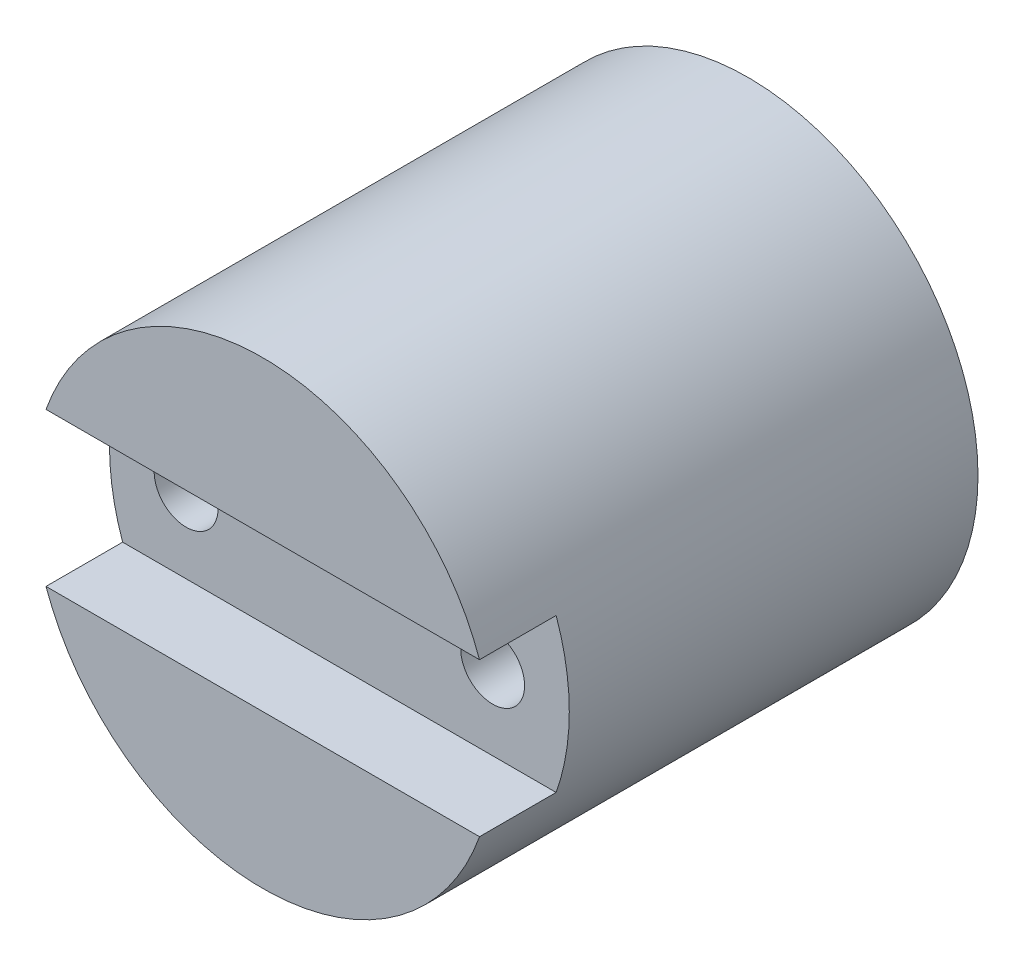
SolidWorks part; units mm, degrees
ref_plane "Front Plane" through (0, 0, 0) normal (0, 0, 1) x (1, 0, 0)
ref_plane "Top Plane" through (0, 0, 0) normal (0, 1, 0) x (1, 0, 0)
ref_plane "Right Plane" through (0, 0, 0) normal (1, 0, 0) x (0, 0, -1)
sketch "Sketch1" plane through (0, 0, 0) normal (0, 0, 1) x (1, 0, 0)
  circle A0 centre (0, 0) radius 9
extrude "Body" add sketch "Sketch1" along normal blind 19
sketch "Sketch2" plane through (0, 0, 0) normal (0, 0, 1) x (1, 0, 0)
  circle A0 centre (0, 0) radius 4
extrude "Bore" cut sketch "Sketch2" along normal blind 12
sketch "Sketch3" plane through (0, 0, 0) normal (0, 0, 1) x (1, 0, 0)
  line L1 (3.2, -4.5) -> (4.7, -4.5)
  line L2 (3.2, -4.5) -> (3.2, 4.5)
  line L3 (3.2, 4.5) -> (4.7, 4.5)
  line L4 (4.7, -4.5) -> (4.7, 4.5)
extrude "Bore_flat" add sketch "Sketch3" along normal blind 12
ref_plane "Plane_z12" through (0, 0, 12) normal (0, 0, 1) x (1, 0, 0)
sketch "Sketch4" plane through (0, 0, 12) normal (0, 0, 1) x (1, 0, 0)
  circle A0 centre (0, 0) radius 3
extrude "Magnet_pocket" cut sketch "Sketch4" along normal blind 3
ref_plane "Plane_z16" through (0, 0, 16) normal (0, 0, 1) x (1, 0, 0)
sketch "Sketch5" plane through (0, 0, 16) normal (0, 0, 1) x (1, 0, 0)
  line L1 (-11, -3) -> (11, -3)
  line L2 (-11, -3) -> (-11, 3)
  line L3 (-11, 3) -> (11, 3)
  line L4 (11, -3) -> (11, 3)
extrude "Arm_slot" cut sketch "Sketch5" along normal blind 3
ref_plane "Plane_z10" through (0, 0, 10) normal (0, 0, 1) x (1, 0, 0)
sketch "Sketch6" plane through (0, 0, 10) normal (0, 0, 1) x (1, 0, 0)
  circle A0 centre (-6, 0) radius 1.25
  circle A1 centre (6, 0) radius 1.25
extrude "Arm_screws" cut sketch "Sketch6" along normal blind 6
